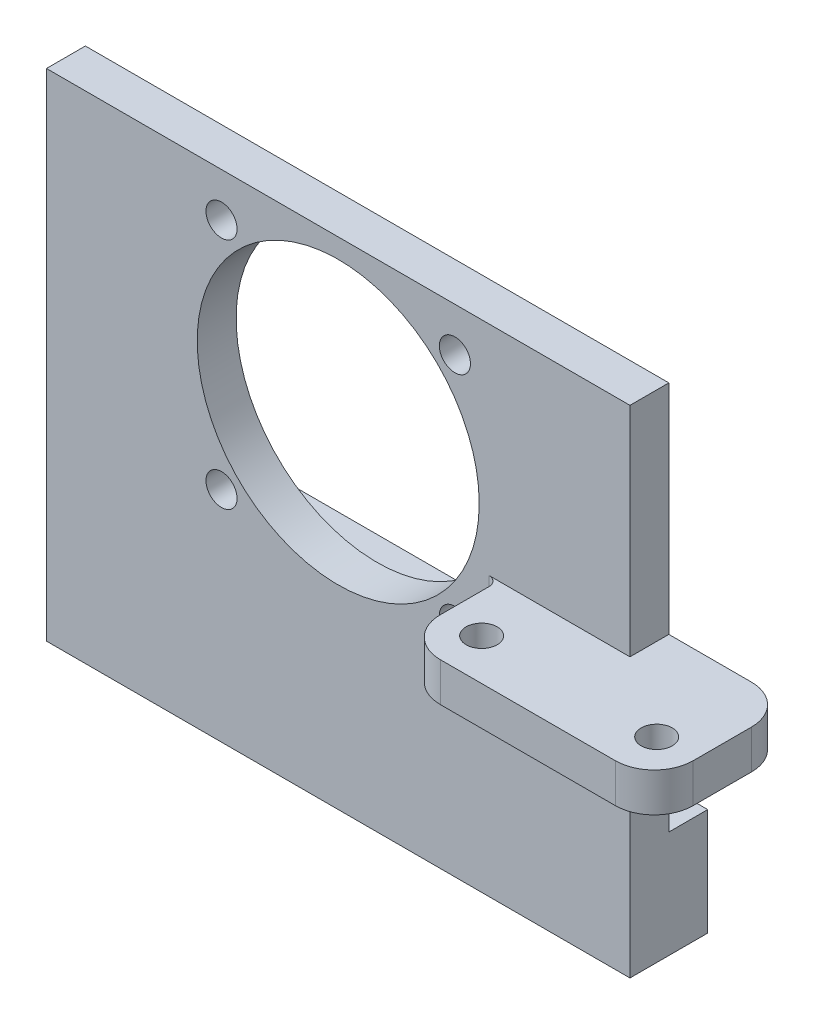
SolidWorks part; units mm, degrees
ref_plane "Płaszczyzna przednia" through (0, 0, 0) normal (0, 0, 1) x (1, 0, 0)
ref_plane "Płaszczyzna górna" through (0, 0, 0) normal (0, 1, 0) x (1, 0, 0)
ref_plane "Płaszczyzna prawa" through (0, 0, 0) normal (1, 0, 0) x (0, 0, -1)
sketch "Sketch1" plane through (0, 0, 0) normal (0, 0, 1) x (1, 0, 0)
  line L1 (0, 0) -> (60, 0)
  line L2 (0, 0) -> (0, 40)
  line L3 (0, 40) -> (60, 40)
  line L4 (60, 0) -> (60, 40)
  line L5 (0, 0) -> (60, 40) construction
  line L6 (0, 40) -> (60, 0) construction
  point P4 (30, 20)
  dimension "D1" = 60
  dimension "D2" = 40
extrude "Boss-Extrude1" add sketch "Sketch1" along normal blind 4
sketch "Sketch4" plane through (0, 0, 4) normal (0, 0, 1) x (1, 0, 0)
  line L0 (0, 40) -> (60, 0) construction
  line L1 (0, 0) -> (60, 40) construction
  line L2 (30, -0.7473) -> (30, 40.7473) construction
  line L3 (60, 40) -> (0, 40) construction
  circle A0 centre (30, 23.5) radius 14.5
  point P10 (30, 20)
  point P16 (30, 20)
  dimension "D1" = 29
  dimension "D2" = 16.5
extrude "Cut-Extrude1" cut sketch "Sketch4" against normal blind 4
sketch "Sketch6" plane through (0, 0, 4) normal (0, 0, 1) x (1, 0, 0)
  circle A0 centre (42, 11.5) radius 1.6
  circle A1 centre (18, 11.5) radius 1.6
  circle A2 centre (18, 35.5) radius 1.6
  circle A3 centre (42, 35.5) radius 1.6
  dimension "D1" = 3.2
  dimension "D2" = 3.2
  dimension "D3" = 3.2
  dimension "D4" = 3.2
extrude "Cut-Extrude2" cut sketch "Sketch6" against normal blind 4
sketch "Sketch7" plane through (0, 0, 4) normal (0, 0, 1) x (1, 0, 0)
  line L0 (56.5, 17.6) -> (62.5, 17.6) construction
  line L1 (46.5, 17.6) -> (72.5, 17.6)
  line L2 (46.5, 17.6) -> (46.5, 13.6)
  line L3 (46.5, 13.6) -> (72.5, 13.6)
  line L4 (72.5, 17.6) -> (72.5, 13.6)
  line L5 (46.5, 17.6) -> (72.5, 13.6) construction
  line L6 (46.5, 13.6) -> (72.5, 17.6) construction
  line L10 (59.5, 13.6) -> (59.5, 17.6) construction
  line L11 (62.5, 17.6) -> (62.5, 20) construction
  point P4 (59.5, 15.6)
  dimension "D1" = 4
  dimension "D2" = 26
  dimension "D3" = 3
extrude "Boss-Extrude3" add sketch "Sketch7" along normal blind 10
sketch "Sketch8" plane through (0, 17.6, 0) normal (0, 1, 0) x (1, 0, 0)
  circle A0 centre (68.5, -9.75) radius 1.6
  circle A1 centre (50.5, -9.75) radius 1.6
extrude "Cut-Extrude3" cut sketch "Sketch8" against normal through all
sketch "Sketch9" plane through (60, 0, 0) normal (1, 0, 0) x (0, 0, -1)
  line L0 (0, 0) -> (0, 40) construction
  line L1 (-4, 13.6) -> (0, 13.6)
  line L2 (-4, 13.6) -> (-4, 17.6)
  line L3 (-4, 17.6) -> (0, 17.6)
  line L4 (0, 13.6) -> (0, 17.6)
  line L5 (-4, 13.6) -> (0, 17.6) construction
  line L6 (-4, 17.6) -> (0, 13.6) construction
  point P4 (-2, 15.6)
extrude "Boss-Extrude4" add sketch "Sketch9" along normal blind 12.5
fillet "Fillet2" radius 4 3 edges at (72.5, 15.6, 14) (46.5, 15.6, 14) (72.5, 15.6, 0)
fillet "Fillet3" radius 1 3 edges at (60, 13.6, 2) (53.25, 13.6, 4) (46.5, 15.6, 4)
sketch "Sketch10" plane through (0, 0, 0) normal (0, -1, 0) x (1, 0, 0)
  line L1 (0, 4) -> (60, 4)
  line L2 (0, 4) -> (0, 0)
  line L3 (0, 0) -> (60, 0)
  line L4 (60, 4) -> (60, 0)
  line L5 (0, 4) -> (60, 0) construction
  line L6 (0, 0) -> (60, 4) construction
  point P4 (30, 2)
extrude "Boss-Extrude5" add sketch "Sketch10" along normal blind 11
sketch "Sketch11" plane through (0, 0, 0) normal (0, 0, -1) x (-1, 0, 0)
  line L0 (-60, -11) -> (-60, 12.6) construction
  line L1 (-60, 10) -> (-47.5, 10)
  line L2 (-60, 10) -> (-60, 6)
  line L3 (-60, 6) -> (0, 6)
  line L4 (0, 10) -> (0, 6)
  line L5 (-60, 10) -> (0, 6) construction
  line L6 (-60, 6) -> (0, 10) construction
  line L7 (0, 40) -> (0, -11) construction
  line L8 (0, -11) -> (-60, -11) construction
  line L9 (-30, 10) -> (-30, 6) construction
  line L10 (-12.5, 10) -> (0, 10)
  line L11 (-45.2515, 7.5) -> (-14.7485, 7.5)
  arc A0 (-47.5, 10) -> (-45.2515, 7.5) centre (-40.5605, 13.9803) ccw
  arc A1 (-12.5, 10) -> (-14.7485, 7.5) centre (-19.4395, 13.9803) cw
  arc A2 (-41.121, 6) -> (-40, 6) centre (-40.5605, 13.9803) ccw
  arc A3 (-18.879, 6) -> (-20, 6) centre (-19.4395, 13.9803) cw
  point P4 (-30, 8)
  point P22 (-30, 7.5)
  line M19 (-60, 12.6) -> (-60, -11)
  line M21 (0, -11) -> (0, 40)
  dimension "D3" = 8
  dimension "D1" = 4
  dimension "D2" = 17
  dimension "D4" = 12.5
  dimension "D5" = 20
  dimension "D6" = 1.5
extrude "Boss-Extrude6" add sketch "Sketch11" along normal blind 4 contours L10 A1 L11 A0 L1 L3 M19 M21 region at (53.75, 9.3987, 0)
fillet "Fillet4" radius 2 4 edges at (47.5, 10, -2) (12.5, 10, -2) (45.2515, 7.5, -2) (14.7485, 7.5, -2)
fillet "Fillet5" radius 1 9 edges at (54.2876, 10, 0) (47.6786, 9.7878, 0) (46.457, 8.5737, 0) (45.263, 7.6309, 0) (30, 7.5, 0) (14.737, 7.6309, 0) (13.543, 8.5737, 0) (12.3214, 9.7878, 0) (5.7124, 10, 0)
sketch "Sketch13" plane through (0, 0, 0) normal (0, 0, -1) x (-1, 0, 0)
  line L0 (-60, -11) -> (-60, 0)
  line L1 (-60, -11) -> (-60, 6) construction
  line L2 (-60, 0) -> (-39, 0)
  line L3 (-60, -11) -> (-33, -11)
  line L4 (0, -11) -> (-60, -11) construction
  line L5 (-33, -11) -> (-33, -6)
  line L6 (-30, 23.5) -> (-30, -11) construction
  line L7 (0, 0) -> (-21, 0)
  line L8 (0, -11) -> (0, 0)
  line L9 (0, -11) -> (-27, -11)
  line L10 (-27, -11) -> (-27, -6)
  arc A0 (-39, 0) -> (-33, -6) centre (-39, -6) cw
  arc A1 (-21, 0) -> (-27, -6) centre (-21, -6) ccw
extrude "Boss-Extrude7" add sketch "Sketch13" along normal blind 4
